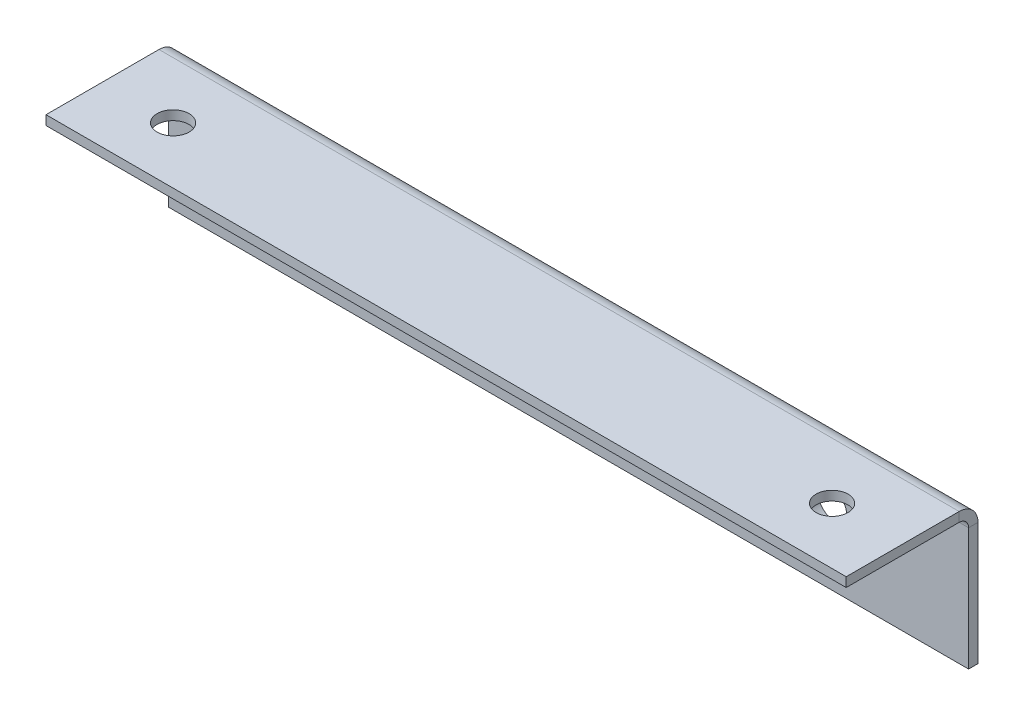
SolidWorks part; units mm, degrees
note: The reader was unsure of these and kept them because the rebuilt part matched: flange length of "Ребро-кромка1".
material "Оцинкованная сталь"
ref_plane "Спереди" through (0, 0, 0) normal (0, 0, 1) x (1, 0, 0)
ref_plane "Сверху" through (0, 0, 0) normal (0, 1, 0) x (1, 0, 0)
ref_plane "Справа" through (0, 0, 0) normal (1, 0, 0) x (0, 0, -1)
sketch "Эскиз1" plane through (0, 0, 0) normal (0, 0, 1) x (1, 0, 0)
  line L5 (42.5, 7.5) -> (-42.5, 7.5)
  line L6 (42.5, 7.5) -> (42.5, -7.5)
  line L7 (42.5, -7.5) -> (-42.5, -7.5)
  line L8 (-42.5, 7.5) -> (-42.5, -7.5)
  line L9 (42.5, 7.5) -> (-42.5, -7.5) construction
  line L10 (42.5, -7.5) -> (-42.5, 7.5) construction
  point P0 (0, 0)
  dimension "D1" = 85
  dimension "D2" = 15
base flange "Базовая кромка1" sketch "Эскиз1" thickness 1 reverse thickness direction no parameters "D1"=1
edge flange "Ребро-кромка1" sketch "Эскиз8" flange angle 90 flange length 14 flange position material inside bend radius 1 thickness 1 relief rectangular parameters "D6"=10
sketch "Эскиз8" plane through (0, 7.5, 0) normal (0, 1, 0) x (-1, 0, 0)
  line L0 (-42.5, 0) -> (42.5, 0) construction
  line L1 (-42.5, 0) -> (42.5, 0)
  line L2 (-42.5, 0) -> (-42.5, 13)
  line L3 (-42.5, 13) -> (42.5, 13)
  line L4 (42.5, 13) -> (42.5, 0)
bend "EdgeBend1" bend radius 1 bend angle 90 parameters "D5"=1
sketch "Эскиз9" plane through (0, 0, 0) normal (0, 0, 1) x (1, 0, 0)
  line L0 (-27.5, 0) -> (27.5, 0) construction
  circle A0 centre (-27.5, 0) radius 2.1
  circle A1 centre (27.5, 0) radius 2.1
  dimension "D1" = 4.2
  dimension "D2" = 55
extrude "Вырез-Вытянуть1" cut sketch "Эскиз9" against normal blind 10
hole_wizard "Отверстие с зазором M31" positions "Эскиз11" profile "Эскиз12" hole size "M3" standard "GOST"
sketch "Эскиз11" plane through (0, 6.5, 0) normal (0, -1, 0) x (-1, 0, 0)
  line L0 (-35, -7) -> (35, -7) construction
  line L3 (0, -7) -> (0, 0) construction
  line L7 (35, -7) -> (42.5, -7) construction
  line L8 (42.5, -1) -> (42.5, -13) construction
  point P0 (-35, -7)
  point P2 (35, -7)
  dimension "D1" = 70
sketch "Эскиз12" plane through (35, 6.5, 7) normal (1, 0, 0) x (0, 0, -1)
  line L0 (0, 0) -> (0, 19.5215)
  line L1 (0, 19.5215) -> (1.7, 18.5)
  line L2 (1.7, 18.5) -> (1.7, 0)
  line L5 (1.7, 0) -> (0, 0)
  line L10 (0, 19.5215) -> (-1.7, 18.5) construction
  line L11 (0, -6.35) -> (0, 107.95) construction
  dimension "Диаметр отверстия" = 3.4
  dimension "Глубина отверстия" = 18.5
  dimension "Угол заточки сверла" = 118
sketch "Сгиб-Линии1" [suppressed] plane through (0, 0, 0) normal (0, 1, 0) x (1, 0, 0)
sketch "Граничная рамка1" [suppressed] plane through (0, 0, 0) normal (0, 1, 0) x (1, 0, 0)
sheet metal parameters "Листовой металл3" thickness 1 parameters "D1"=1
flat pattern "Развертка3" [suppressed]
sketch "Сгиб-Линии2" plane through (0, 0, 0) normal (0, 1, 0) x (1, 0, 0)
sketch "Граничная рамка2" [suppressed] plane through (0, 0, 0) normal (0, 1, 0) x (1, 0, 0)
sheet metal parameters "Листовой металл4" thickness 1 parameters "D1"=1
flat pattern "Развертка3" [suppressed]
sketch "Сгиб-Линии2" plane through (0, 0, 0) normal (0, 1, 0) x (1, 0, 0)
sketch "Граничная рамка2" [suppressed] plane through (0, 0, 0) normal (0, 1, 0) x (1, 0, 0)
bend of the flat pattern "Плоское состояние-<EdgeBend1>1"
sheet metal parameters "Листовой металл5" thickness 1 parameters "D1"=1
flat pattern "Развертка3" [suppressed]
sketch "Сгиб-Линии2" plane through (0, 0, 0) normal (0, 1, 0) x (1, 0, 0)
sketch "Граничная рамка2" [suppressed] plane through (0, 0, 0) normal (0, 1, 0) x (1, 0, 0)
bend of the flat pattern "Плоское состояние-<EdgeBend1>1"
sheet metal parameters "Листовой металл6" thickness 1 parameters "D1"=1
flat pattern "Развертка3"
sketch "Сгиб-Линии2" plane through (0, 0, 0) normal (0, 0, 1) x (1, 0, 0)
  line L0 (-42.5, 7.0708) -> (42.5, 7.0708) construction
  line L1 (-42.5, 7.0708) -> (42.5, 7.0708) construction
sketch3d "Граничная рамка2" [suppressed]
  line L0 (-42.5, -7.5, 0) -> (42.5, -7.5, 0) construction
  line L1 (-42.5, 20.6416, 0) -> (42.5, 20.6416, 0) construction
  line L2 (-42.5, -7.5, 0) -> (-42.5, 20.6416, 0) construction
  line L3 (42.5, -7.5, 0) -> (42.5, 20.6416, 0) construction
bend of the flat pattern "Плоское состояние-<EdgeBend1>1"
